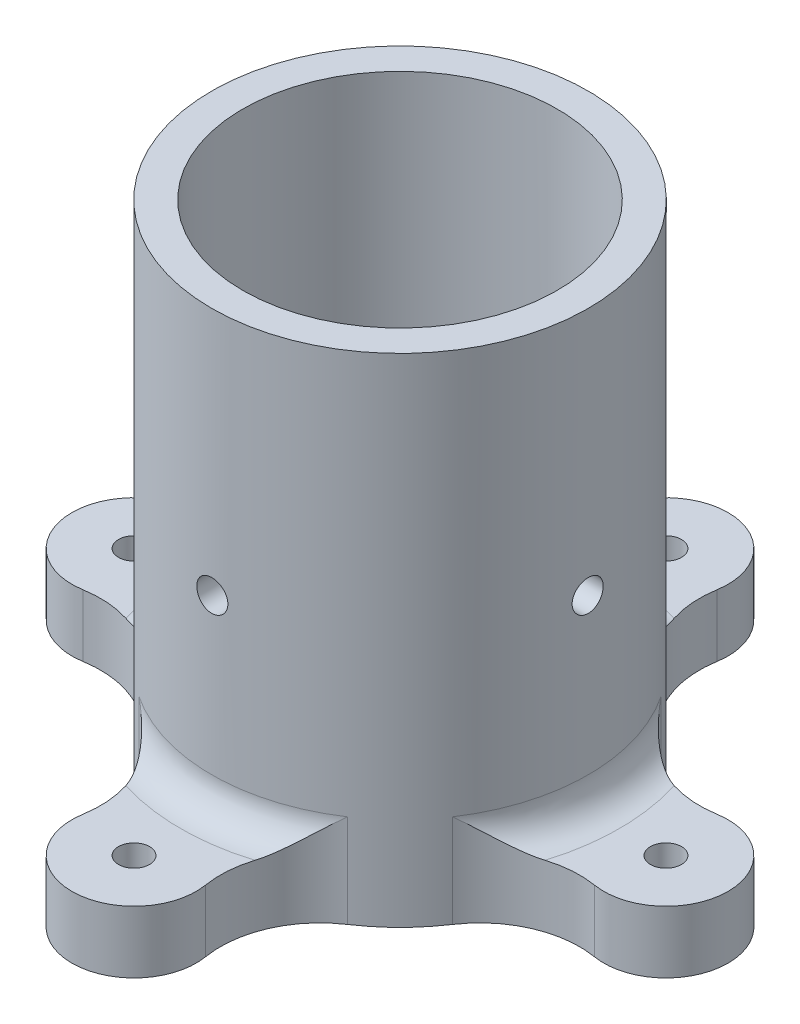
SolidWorks part; units mm, degrees
ref_plane "Front Plane" through (0, 0, 0) normal (0, 0, 1) x (1, 0, 0)
ref_plane "Top Plane" through (0, 0, 0) normal (0, 1, 0) x (1, 0, 0)
ref_plane "Right Plane" through (0, 0, 0) normal (1, 0, 0) x (0, 0, -1)
sketch "Sketch1" plane through (0, 0, 0) normal (0, 1, 0) x (1, 0, 0)
  circle A0 centre (0, 0) radius 31.75 construction
  circle A1 centre (0, 0) radius 32.131
  circle A2 centre (0, 0) radius 38.481
  dimension "D1" = 63.5
  dimension "D2" = 0.381
  dimension "D3" = 6.35
extrude "Boss-Extrude1" add sketch "Sketch1" along normal blind 101.6
sketch "Sketch2" plane through (0, 0, 0) normal (0, -1, 0) x (1, 0, 0)
  line L0 (0, 0) -> (0, 54.356) construction
  line L1 (-15.1614, 38.481) -> (15.1614, 38.481) construction
  line L2 (12.3775, 51.181) -> (-12.3775, 51.181) construction
  circle A0 centre (0, 54.356) radius 3.175
  arc A1 (-12.5289, 52.278) -> (12.5289, 52.278) centre (0, 54.356) cw
  arc A2 (-12.5289, 52.278) -> (-21.318, 32.0364) centre (-32.575, 48.9533) cw
  circle A3 centre (0, 0) radius 38.481 construction
  arc A4 (12.5289, 52.278) -> (21.318, 32.0364) centre (32.575, 48.9533) ccw
  arc A5 (52.278, 12.5289) -> (32.0364, 21.318) centre (48.9533, 32.575) cw
  arc A6 (52.278, 12.5289) -> (52.278, -12.5289) centre (54.356, 0) cw
  circle A7 centre (54.356, 0) radius 3.175
  arc A8 (52.278, -12.5289) -> (32.0364, -21.318) centre (48.9533, -32.575) ccw
  arc A9 (12.5289, -52.278) -> (21.318, -32.0364) centre (32.575, -48.9533) cw
  arc A10 (12.5289, -52.278) -> (-12.5289, -52.278) centre (0, -54.356) cw
  circle A11 centre (0, -54.356) radius 3.175
  arc A12 (-12.5289, -52.278) -> (-21.318, -32.0364) centre (-32.575, -48.9533) ccw
  arc A13 (-52.278, -12.5289) -> (-32.0364, -21.318) centre (-48.9533, -32.575) cw
  arc A14 (-52.278, -12.5289) -> (-52.278, 12.5289) centre (-54.356, 0) cw
  circle A15 centre (-54.356, 0) radius 3.175
  arc A16 (-52.278, 12.5289) -> (-32.0364, 21.318) centre (-48.9533, 32.575) ccw
  point P33 (0, 0)
  dimension "D1" = 6.35
  dimension "D2" = 9.525
  dimension "D4" = 20.32
  dimension "D3" = 12.7
  dimension "D5" = 4
extrude "Boss-Extrude2" add sketch "Sketch2" against normal blind 12.7
sketch "Sketch3" plane through (0, 0, 0) normal (0, 0, 1) x (1, 0, 0)
  line L0 (0, 0) -> (0, 50.8) construction
  line L1 (0, 50.8) -> (0, 101.6) construction
  line L2 (38.481, 101.6) -> (-38.481, 101.6) construction
  circle A0 centre (0, 50.8) radius 3.175
  dimension "D2" = 6.35
  dimension "D1" = 50.8
extrude "Cut-Extrude1" cut sketch "Sketch3" against normal through all both and the other way through all
pattern_circular "CirPattern1" count 4 over 360 about axis through (0, 101.6, 0) along (0, -1, 0) of "Cut-Extrude1"
fillet "Fillet1" radius 6.35 4 edges at (38.481, 12.7, 0) (0, 12.7, 38.481) (0, 12.7, -38.481) (-38.481, 12.7, 0)
